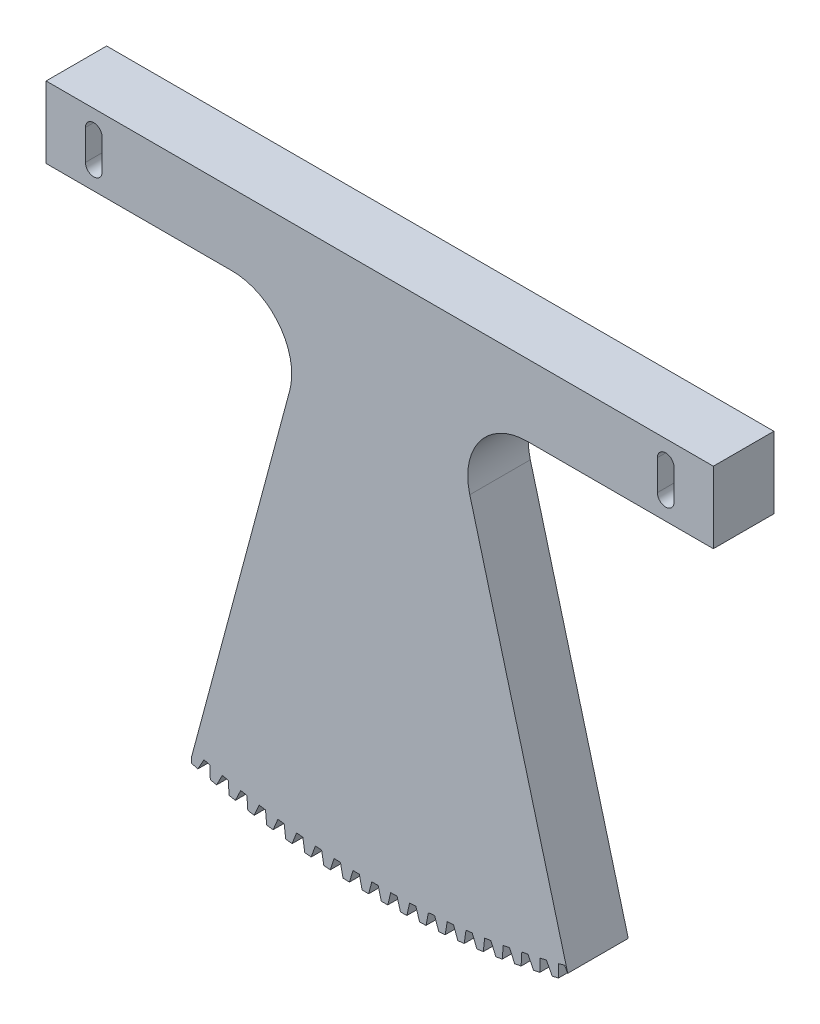
SolidWorks part; units mm, degrees
ref_plane "Front Plane" through (0, 0, 0) normal (0, 0, 1) x (1, 0, 0)
ref_plane "Top Plane" through (0, 0, 0) normal (0, 1, 0) x (1, 0, 0)
ref_plane "Right Plane" through (0, 0, 0) normal (1, 0, 0) x (0, 0, -1)
sketch "Sketch3" plane through (0, 0, 0) normal (0, 0, 1) x (1, 0, 0)
  line L0 (0, 0) -> (0, -304.8) construction
  line L1 (-21.234, -79.2464) -> (-78.888, -294.4142)
  line L2 (21.234, -79.2464) -> (78.888, -294.4142)
  line L4 (-140, -79.56) -> (140, -79.56)
  line L5 (-140, -79.56) -> (-140, -109.56)
  line L6 (-140, -109.56) -> (140, -109.56)
  line L7 (140, -79.56) -> (140, -109.56)
  line L8 (0, -109.56) -> (0, -79.56) construction
  line L9 (-140, -94.56) -> (140, -94.56) construction
  arc A0 (-78.888, -294.4142) -> (78.888, -294.4142) centre (0, 0) ccw
  point P269 (0, -94.56)
  dimension "D1" = 304.8
  dimension "D4" = 79.56
  dimension "D5" = 30
  dimension "D6" = 280
  dimension "D7" = 140
extrude "Boss-Extrude2" add sketch "Sketch3" along normal blind 25.4 contours L7 L4 L2 L6 | L1 L6 L2 L4 | L1 L4 L2 | L5 L6 L1 L4 | L1 A0 L2 L6 region at (0, -95.3531, 0) region at (-82.6452, -94.3847, 0) region at (0, -220.3694, 0) region at (82.6452, -94.3847, 0)
fillet "Fillet1" radius 25 2 edges at (-29.3565, -109.56, 12.7) (29.3565, -109.56, 12.7)
sketch "Sketch4" plane through (0, -79.56, 0) normal (0, 1, 0) x (1, 0, 0)
  line L1 (-140, 0) -> (140, 0)
  line L2 (-140, 0) -> (-140, -25.4)
  line L3 (-140, -25.4) -> (140, -25.4)
  line L4 (140, 0) -> (140, -25.4)
  line L5 (0, -25.4) -> (0, 0) construction
  line L6 (-140, -12.7) -> (140, -12.7) construction
  point P252 (0, -12.7)
sketch "Sketch5" plane through (0, 0, 0) normal (0, 0, -1) x (-1, 0, 0)
  line L0 (-123.5, -94.56) -> (-123.5, -100.91)
  line L1 (-116.5, -94.56) -> (-116.5, -100.91)
  line L2 (116.5, -94.56) -> (116.5, -88.21)
  line L3 (140, -79.56) -> (-140, -79.56) construction
  line L4 (-120, -88.21) -> (-120, -100.91) construction
  line L5 (0, -79.56) -> (0, -109.56) construction
  line L6 (-116.5, -94.56) -> (-116.5, -88.21)
  line L7 (-123.5, -94.56) -> (-123.5, -88.21)
  line L8 (116.5, -94.56) -> (116.5, -100.91)
  line L9 (123.5, -94.56) -> (123.5, -100.91)
  line L10 (123.5, -94.56) -> (123.5, -88.21)
  line L11 (-140, -79.56) -> (-140, -109.56) construction
  line L12 (120, -88.21) -> (120, -100.91) construction
  arc A1 (-116.5, -88.21) -> (-123.5, -88.21) centre (-120, -88.21) ccw
  arc A2 (-123.5, -100.91) -> (-116.5, -100.91) centre (-120, -100.91) ccw
  arc A3 (123.5, -100.91) -> (116.5, -100.91) centre (120, -100.91) cw
  arc A4 (116.5, -88.21) -> (123.5, -88.21) centre (120, -88.21) cw
  dimension "D1" = 16.5
  dimension "D2" = 7
  dimension "D3" = 8.65
  dimension "D5" = 3.5
  dimension "D4" = 6.35
sketch "Sketch13" plane through (0, 0, 0) normal (0, 0, -1) x (-1, 0, 0)
  line L0 (0, 0) -> (78.888, -294.4142)
  line L1 (0, 0) -> (-78.888, -294.4142)
  arc A0 (-78.888, -294.4142) -> (78.888, -294.4142) centre (0, 0) ccw
  arc A1 (-78.888, -294.4142) -> (78.888, -294.4142) centre (0, 0) ccw construction
  arc A2 (-78.888, -294.4142) -> (78.888, -294.4142) centre (0, 0) ccw
  dimension "D1" = 609.6
sketch "Sketch14" plane through (0, 0, 0) normal (0, 0, -1) x (-1, 0, 0)
  line L0 (0, 0) -> (80.0203, -298.6399) construction
  line L2 (78.888, -294.4142) -> (78.9109, -297.0369)
  line L3 (78.9109, -297.0369) -> (76.2891, -297.7211)
  line L18 (76.2891, -297.7211) -> (75.0275, -295.4216)
  line L20 (0, 0) -> (-79.2746, -295.8555) construction
  line L32 (78.888, -294.4142) -> (75.0275, -295.4216)
  line L33 (75.0275, -295.4216) -> (78.888, -294.4142)
  line L34 (0, 0) -> (-75.3952, -296.8678) construction
  line L35 (0, 0) -> (-71.5028, -297.8293) construction
  line L36 (0, 0) -> (-67.5982, -298.7397) construction
  line L37 (0, 0) -> (-63.6821, -299.5989) construction
  line L38 (0, 0) -> (-59.755, -300.4068) construction
  line L39 (0, 0) -> (-55.8176, -301.1633) construction
  line L40 (0, 0) -> (-51.8707, -301.8681) construction
  line L41 (0, 0) -> (-47.9149, -302.5212) construction
  line L42 (0, 0) -> (-43.951, -303.1225) construction
  line L43 (0, 0) -> (-39.9794, -303.6718) construction
  line L44 (0, 0) -> (-36.0011, -304.1691) construction
  line L45 (0, 0) -> (-32.0165, -304.6143) construction
  line L46 (0, 0) -> (-28.0265, -305.0073) construction
  line L47 (0, 0) -> (-24.0316, -305.348) construction
  line L48 (0, 0) -> (-20.0327, -305.6364) construction
  line L49 (0, 0) -> (-16.0303, -305.8724) construction
  line L50 (0, 0) -> (-12.0252, -306.0561) construction
  line L51 (0, 0) -> (-8.018, -306.1873) construction
  line L52 (0, 0) -> (-4.0094, -306.266) construction
  line L53 (0, 0) -> (-0.0002, -306.2922) construction
  line L54 (0, 0) -> (4.0091, -306.266) construction
  line L55 (0, 0) -> (8.0176, -306.1873) construction
  line L56 (0, 0) -> (12.0248, -306.0561) construction
  line L57 (0, 0) -> (16.03, -305.8725) construction
  line L58 (0, 0) -> (20.0323, -305.6364) construction
  line L59 (0, 0) -> (24.0313, -305.348) construction
  line L60 (0, 0) -> (28.0261, -305.0073) construction
  line L61 (0, 0) -> (32.0162, -304.6143) construction
  line L62 (0, 0) -> (36.0007, -304.1691) construction
  line L63 (0, 0) -> (39.9791, -303.6719) construction
  line L64 (0, 0) -> (43.9506, -303.1225) construction
  line L65 (0, 0) -> (47.9146, -302.5213) construction
  line L66 (0, 0) -> (51.8704, -301.8682) construction
  line L67 (0, 0) -> (55.8173, -301.1633) construction
  line L68 (0, 0) -> (59.7546, -300.4069) construction
  line L69 (0, 0) -> (63.6817, -299.599) construction
  line L70 (0, 0) -> (67.5979, -298.7398) construction
  line L71 (0, 0) -> (71.5025, -297.8293) construction
  line L72 (0, 0) -> (75.3948, -296.8679) construction
  line L73 (0, 0) -> (-79.2746, -295.8555) construction
  line L74 (0, 0) -> (-75.3952, -296.8678) construction
  line L137 (37.789, -141.0305) -> (78.888, -294.4142) construction
  line L138 (-140, -79.56) -> (-140, -109.56)
  line L139 (-140, -109.56) -> (-61.9371, -109.56)
  line L140 (-37.789, -141.0305) -> (-78.888, -294.4142)
  line L141 (78.888, -294.4142) -> (37.789, -141.0305)
  line L142 (61.9371, -109.56) -> (140, -109.56)
  line L143 (140, -109.56) -> (140, -79.56)
  line L144 (140, -79.56) -> (-140, -79.56)
  line L145 (-140, -79.56) -> (-140, -109.56)
  line L146 (-140, -109.56) -> (-61.9371, -109.56)
  line L147 (-37.789, -141.0305) -> (-78.888, -294.4142)
  line L149 (61.9371, -109.56) -> (140, -109.56)
  line L150 (140, -109.56) -> (140, -79.56)
  line L151 (140, -79.56) -> (-140, -79.56)
  circle A0 centre (0, 0) radius 307.34
  circle A1 centre (0, 0) radius 302.26
  arc A3 (-37.789, -141.0305) -> (-61.9371, -109.56) centre (-61.9371, -134.56) ccw
  arc A5 (61.9371, -109.56) -> (37.789, -141.0305) centre (61.9371, -134.56) ccw
  arc A6 (-37.789, -141.0305) -> (-61.9371, -109.56) centre (-61.9371, -134.56) ccw
  arc A8 (61.9371, -109.56) -> (37.789, -141.0305) centre (61.9371, -134.56) ccw
  arc A11 (-78.888, -294.4142) -> (78.888, -294.4142) centre (0, 0) ccw
  arc A12 (-78.888, -294.4142) -> (78.888, -294.4142) centre (0, 0) ccw
  arc M181 (-78.888, -294.4142) -> (78.888, -294.4142) centre (0, 0) ccw
  dimension "D5" = 614.68
  dimension "D6" = 30
  dimension "D7" = 40
  dimension "D4" = 604.52
  dimension "D1" = 14.5
  dimension "D3" = 14.5
  dimension "D8" = 0.75
  dimension "D9" = 306.2922
  dimension "D10" = 0.75
  dimension "D2" = 0
extrude "Boss-Extrude4" add sketch "Sketch14" against normal up to surface (25.4 mm away) contours L2 M181 region at (-77.2591, -296.0724, 0) up to face at (0, -146.6727, 25.4)
sketch "Sketch15" plane through (0, 0, 0) normal (1, 0, 0) x (0, 0, -1)
  line L0 (0, 0) -> (-23.3364, 0) construction
sketch "Sketch16" plane through (0, 0, 0) normal (0, 0, -1) x (-1, 0, 0)
  line L0 (75.0275, -295.4216) -> (73.7653, -293.1208)
  line L1 (73.7653, -293.1208) -> (71.1999, -293.7544)
  line L2 (71.1999, -293.7544) -> (71.1541, -296.3784)
  line L3 (0, 0) -> (71.5025, -297.8293) construction
  line L4 (0, 0) -> (75.3948, -296.8679) construction
  circle A0 centre (0, 0) radius 302.26 construction
  arc A1 (-78.888, -294.4142) -> (78.888, -294.4142) centre (0, 0) ccw construction
  dimension "D1" = 14.5
  dimension "D2" = 14.5
extrude "Cut-Extrude2" cut sketch "Sketch16" against normal through all and the other way through all
pattern_circular "CirPattern8" count 20 every 1.5 about axis through (0, 0, 0) along (0, 0, 1) of "Cut-Extrude2", "Boss-Extrude4"
extrude "Cut-Extrude3" cut sketch "Sketch5" against normal through all
equation "\"D7@Sketch3\"=\"D6@Sketch3\"/2"
